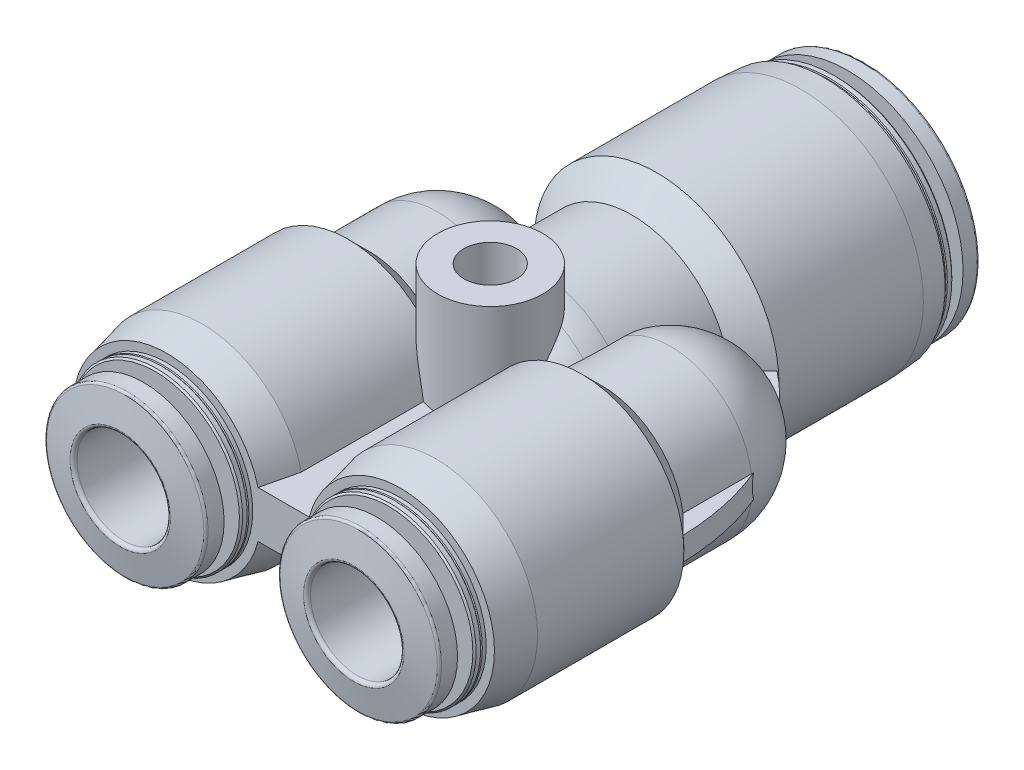
SolidWorks part; units mm, degrees
material "Kunstoff schwarz"
ref_plane "Vorne" through (0, 0, 0) normal (0, 0, 1) x (1, 0, 0)
ref_plane "Oben" through (0, 0, 0) normal (0, 1, 0) x (1, 0, 0)
ref_plane "Rechts" through (0, 0, 0) normal (1, 0, 0) x (0, 0, -1)
ref_plane "Ebene1" through (0, 0, 0) normal (1, 0, 0) x (0, 0, -1)
sketch "Skizze1" plane through (0, 0, 0) normal (1, 0, 0) x (0, 0, -1)
  line L0 (-3, 0) -> (-3, 1)
  line L1 (-3, 1) -> (-1, 1)
  line L2 (-1, 1) -> (-1, 4.2849)
  line L3 (4, 8.4) -> (12.14, 8.4)
  line L4 (12.14, 8.4) -> (14.24, 10.5)
  line L5 (14.24, 10.5) -> (26.6, 10.5)
  line L6 (26.6, 10.5) -> (28.6, 10.3601)
  line L7 (28.6, 10.3601) -> (28.6, 10.08)
  line L8 (28.6, 10.08) -> (28.9293, 10.08)
  line L9 (28.9293, 10.08) -> (29, 10.0093)
  line L10 (29, 10.0093) -> (29.0707, 10.08)
  line L11 (29.0707, 10.08) -> (29.4586, 10.08)
  line L12 (29.4586, 10.08) -> (29.6, 9.9386)
  line L13 (29.6, 9.9386) -> (29.6, 6.7)
  line L14 (29.6, 6.7) -> (30.225, 6.7)
  line L15 (30.6, 7.075) -> (30.6, 9.9)
  line L16 (30.6, 9.9) -> (31.7974, 9.9)
  line L17 (31.9944, 9.7347) -> (32.6, 6.3)
  line L18 (32.6, 6.3) -> (32.6, 0)
  line L19 (32.6, 0) -> (-3, 0)
  line L20 (32.6, 0) -> (-3, 0) construction
  arc A0 (-1, 4.2849) -> (2.0909, 8.1802) centre (3, 4.2849) cw
  arc A1 (2.0909, 8.1802) -> (4, 8.4) centre (4, 0) cw
  arc A2 (30.225, 6.7) -> (30.6, 7.075) centre (30.225, 7.075) ccw
  arc A3 (31.7974, 9.9) -> (31.9944, 9.7347) centre (31.7974, 9.7) cw
revolve "Rotation1" add sketch "Skizze1" angle 360 about L20
ref_plane "Ebene2" through (0, 0, 0) normal (0, 1, 0) x (1, 0, 0)
sketch "Skizze2" plane through (0, 0, 0) normal (0, 1, 0) x (1, 0, 0)
  line L0 (-3, -17.7) -> (3, -17.7)
  line L1 (3, -17.7) -> (3, 0)
  line L2 (3, 0) -> (-3, 0)
  line L3 (-3, 0) -> (-3, -17.7)
extrude "Aufsatz-Linear austragen1" add sketch "Skizze2" against normal blind 2 and the other way blind 2
ref_plane "Ebene3" through (-10, 0, 0) normal (1, 0, 0) x (0, 0, -1)
sketch "Skizze3" plane through (-10, 0, 0) normal (1, 0, 0) x (0, 0, -1)
  line L0 (-21.7, 0) -> (-21.7, 4.3)
  line L1 (-21.7, 4.3) -> (-21.2707, 6.7347)
  line L2 (-21.0737, 6.9) -> (-19.7, 6.9)
  line L3 (-19.7, 6.9) -> (-19.7, 5.075)
  line L4 (-19.325, 4.7) -> (-18.7, 4.7)
  line L5 (-18.7, 4.7) -> (-18.7, 7.2086)
  line L6 (-18.7, 7.2086) -> (-18.5586, 7.35)
  line L7 (-18.5586, 7.35) -> (-18.1707, 7.35)
  line L8 (-18.1707, 7.35) -> (-18.1, 7.2793)
  line L9 (-18.1, 7.2793) -> (-18.0293, 7.35)
  line L10 (-18.0293, 7.35) -> (-17.7, 7.35)
  line L11 (-17.7, 7.35) -> (-17.7, 8.0574)
  line L12 (-17.7, 8.0574) -> (-14.7, 8.75)
  line L13 (-14.7, 8.75) -> (-2.17, 8.75)
  line L14 (-2.17, 8.75) -> (-0.42, 7)
  line L15 (-0.42, 7) -> (5.45, 7)
  line L16 (12.45, 0) -> (-21.7, 0)
  line L17 (12.45, 0) -> (-21.7, 0) construction
  arc A0 (-21.2707, 6.7347) -> (-21.0737, 6.9) centre (-21.0737, 6.7) cw
  arc A1 (-19.7, 5.075) -> (-19.325, 4.7) centre (-19.325, 5.075) ccw
  arc A2 (5.45, 7) -> (12.45, 0) centre (5.45, 0) cw
revolve "Rotation2" add sketch "Skizze3" angle 360 about L17 reverse direction yes
ref_plane "Ebene4" through (10, 0, 0) normal (1, 0, 0) x (0, 0, -1)
sketch "Skizze4" plane through (10, 0, 0) normal (1, 0, 0) x (0, 0, -1)
  line L0 (-21.7, 0) -> (-21.7, 4.3)
  line L1 (-21.7, 4.3) -> (-21.2707, 6.7347)
  line L2 (-21.0737, 6.9) -> (-19.7, 6.9)
  line L3 (-19.7, 6.9) -> (-19.7, 5.075)
  line L4 (-19.325, 4.7) -> (-18.7, 4.7)
  line L5 (-18.7, 4.7) -> (-18.7, 7.2086)
  line L6 (-18.7, 7.2086) -> (-18.5586, 7.35)
  line L7 (-18.5586, 7.35) -> (-18.1707, 7.35)
  line L8 (-18.1707, 7.35) -> (-18.1, 7.2793)
  line L9 (-18.1, 7.2793) -> (-18.0293, 7.35)
  line L10 (-18.0293, 7.35) -> (-17.7, 7.35)
  line L11 (-17.7, 7.35) -> (-17.7, 8.0574)
  line L12 (-17.7, 8.0574) -> (-14.7, 8.75)
  line L13 (-14.7, 8.75) -> (-2.17, 8.75)
  line L14 (-2.17, 8.75) -> (-0.42, 7)
  line L15 (-0.42, 7) -> (5.45, 7)
  line L16 (12.45, 0) -> (-21.7, 0)
  line L17 (12.45, 0) -> (-21.7, 0) construction
  arc A0 (-21.2707, 6.7347) -> (-21.0737, 6.9) centre (-21.0737, 6.7) cw
  arc A1 (-19.7, 5.075) -> (-19.325, 4.7) centre (-19.325, 5.075) ccw
  arc A2 (5.45, 7) -> (12.45, 0) centre (5.45, 0) cw
revolve "Rotation3" add sketch "Skizze4" angle 360 about L17 reverse direction yes
ref_plane "Ebene5" through (0, 0, 0) normal (0, 1, 0) x (1, 0, 0)
sketch "Skizze5" plane through (0, 0, 0) normal (0, 1, 0) x (1, 0, 0)
  line L0 (-18.55, -2.17) -> (18.55, -2.17)
  line L1 (10.3, 14.24) -> (-10.3, 14.24)
  arc A0 (18.55, -2.17) -> (10.3, 14.24) centre (-2.5343, -2.4912) ccw
  arc A1 (-10.3, 14.24) -> (-18.55, -2.17) centre (2.5343, -2.4912) ccw
extrude "Aufsatz-Linear austragen2" add sketch "Skizze5" against normal blind 1 and the other way blind 1
ref_plane "Ebene6" through (0, 0, 0) normal (1, 0, 0) x (0, 0, -1)
sketch "Skizze6" plane through (0, 0, 0) normal (1, 0, 0) x (0, 0, -1)
  line L0 (0, 10.85) -> (4.5, 10.85)
  line L1 (4.5, 10.85) -> (4.5, -10.85)
  line L2 (4.5, -10.85) -> (0, -10.85)
  line L3 (0, -10.85) -> (0, 10.85)
  line L4 (0, -10.85) -> (0, 10.85) construction
revolve "Rotation4" add sketch "Skizze6" angle 360 about L4 reverse direction yes
ref_plane "Ebene7" through (0, 0, 0) normal (1, 0, 0) x (0, 0, -1)
sketch "Skizze7" plane through (0, 0, 0) normal (1, 0, 0) x (0, 0, -1)
  line L0 (0, 10.85) -> (2.25, 10.85)
  line L1 (2.25, 10.85) -> (2.25, -10.85)
  line L2 (2.25, -10.85) -> (0, -10.85)
  line L3 (0, -10.85) -> (0, 10.85)
  line L4 (0, -10.85) -> (0, 10.85) construction
revolve "Schnitt-Rotation1" cut sketch "Skizze7" angle 360 about L4 reverse direction yes
ref_plane "Ebene8" through (-10, 0, 0) normal (1, 0, 0) x (0, 0, -1)
sketch "Skizze8" plane through (-10, 0, 0) normal (1, 0, 0) x (0, 0, -1)
  line L0 (-21.7, 0) -> (-21.7, 4.3)
  line L1 (-21.4, 4) -> (-3.6, 4)
  line L2 (-3.6, 4) -> (-3.6, 0)
  line L3 (-3.6, 0) -> (-21.7, 0)
  line L4 (-3.6, 0) -> (-21.7, 0) construction
  arc A0 (-21.7, 4.3) -> (-21.4, 4) centre (-21.4, 4.3) ccw
revolve "Schnitt-Rotation2" cut sketch "Skizze8" angle 360 about L4
ref_plane "Ebene9" through (10, 0, 0) normal (1, 0, 0) x (0, 0, -1)
sketch "Skizze9" plane through (10, 0, 0) normal (1, 0, 0) x (0, 0, -1)
  line L0 (-21.7, 0) -> (-21.7, 4.3)
  line L1 (-21.4, 4) -> (-3.6, 4)
  line L2 (-3.6, 4) -> (-3.6, 0)
  line L3 (-3.6, 0) -> (-21.7, 0)
  line L4 (-3.6, 0) -> (-21.7, 0) construction
  arc A0 (-21.7, 4.3) -> (-21.4, 4) centre (-21.4, 4.3) ccw
revolve "Schnitt-Rotation3" cut sketch "Skizze9" angle 360 about L4
ref_plane "Ebene10" through (0, 0, 0) normal (1, 0, 0) x (0, 0, -1)
sketch "Skizze10" plane through (0, 0, 0) normal (1, 0, 0) x (0, 0, -1)
  line L0 (9.2, 0) -> (9.2, 6)
  line L1 (9.2, 6) -> (32.3, 6)
  line L2 (32.6, 6.3) -> (32.6, 0)
  line L3 (32.6, 0) -> (9.2, 0)
  line L4 (32.6, 0) -> (9.2, 0) construction
  arc A0 (32.3, 6) -> (32.6, 6.3) centre (32.3, 6.3) ccw
revolve "Schnitt-Rotation4" cut sketch "Skizze10" angle 360 about L4
sketch "Skizze11" plane through (0, 0, 0) normal (0, 1, 0) x (1, 0, 0)
